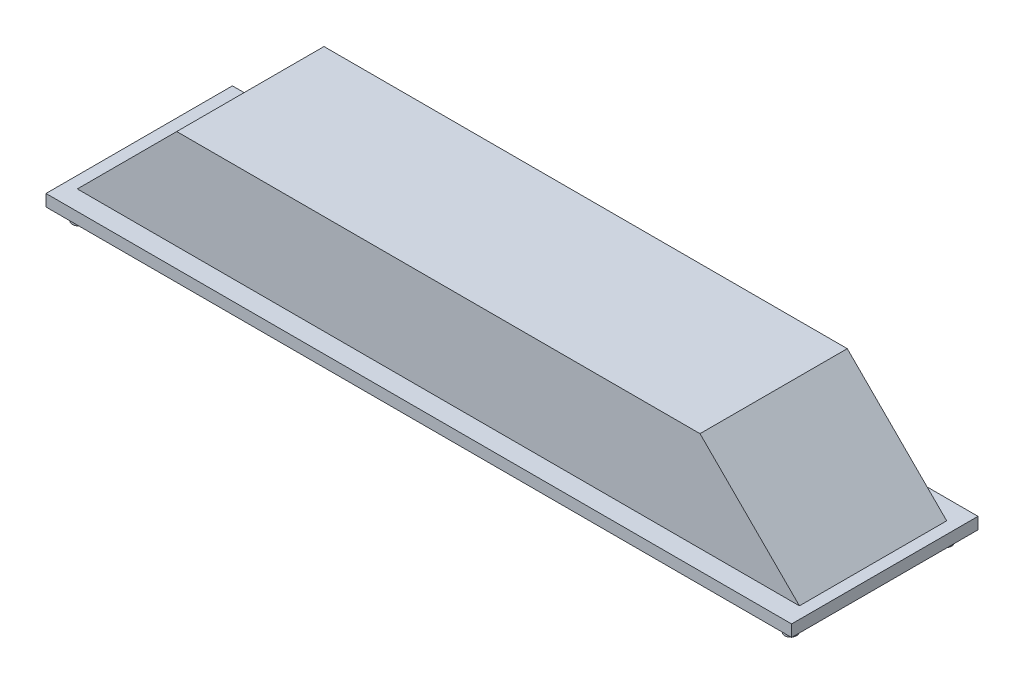
SolidWorks part; units mm, degrees
material "Custom Plastic"
ref_plane "Front Plane" through (0, 0, 0) normal (0, 0, 1) x (1, 0, 0)
ref_plane "Top Plane" through (0, 0, 0) normal (0, 1, 0) x (1, 0, 0)
ref_plane "Right Plane" through (0, 0, 0) normal (1, 0, 0) x (0, 0, -1)
sketch "Sketch1" plane through (0, 0, 0) normal (0, 1, 0) x (1, 0, 0)
  line L1 (-38.1, 9.525) -> (38.1, 9.525)
  line L2 (-38.1, 9.525) -> (-38.1, -9.525)
  line L3 (-38.1, -9.525) -> (38.1, -9.525)
  line L4 (38.1, 9.525) -> (38.1, -9.525)
  line L5 (-38.1, 9.525) -> (38.1, -9.525) construction
  line L6 (-38.1, -9.525) -> (38.1, 9.525) construction
  point P0 (0, 0)
  dimension "D1" = 19.05
  dimension "D2" = 76.2
extrude "Boss-Extrude1" add sketch "Sketch1" along normal blind 1.2
sketch "Sketch2" plane through (0, 0, 9.525) normal (0, 0, 1) x (1, 0, 0)
  line L0 (-36.9, 1.2) -> (-26.74, 11.36)
  line L1 (-38.1, 1.2) -> (38.1, 1.2) construction
  line L2 (-26.74, 11.36) -> (26.74, 11.36)
  line L3 (26.74, 11.36) -> (36.9, 1.2)
  line L4 (36.9, 1.2) -> (-36.9, 1.2)
  dimension "D1" = 1.2
  dimension "D2" = 1.2
  dimension "D3" = 10.16
  dimension "D4" = 45
  dimension "D5" = 45
extrude "Boss-Extrude2" add sketch "Sketch2" against normal offset from surface (15.05 mm away) 2 from offset 2 up to face at (0, 0.6, -9.525) offset against normal yes
shell "Shell1" thickness 1.2 removed face at (0, 0, 0)
sketch "Sketch3" plane through (0, 0, 0) normal (0, -1, 0) x (1, 0, 0)
  line L0 (-38.1, 9.525) -> (38.1, 9.525) construction
  line L1 (-36.4029, -6.325) -> (-36.4029, 6.325) construction
  line L2 (-38.1, -9.525) -> (-38.1, 9.525) construction
  circle A0 centre (-36.4029, 7.9241) radius 0.6
  dimension "D2" = 1.2
  dimension "D1" = 1.6009
  dimension "D3" = 1.6971
extrude "Boss-Extrude3" add sketch "Sketch3" along normal blind 1.2
mirror "Mirror1" about plane through (0, 0, 0) normal (0, 0, 1) of "Boss-Extrude3"
mirror "Mirror2" about plane through (0, 0, 0) normal (1, 0, 0) of "Mirror1", "Boss-Extrude3"
equation "\"D5@Sketch2\"=\"D4@Sketch2\""
equation "\"D2@Sketch2\"=\"D1@Sketch2\""
